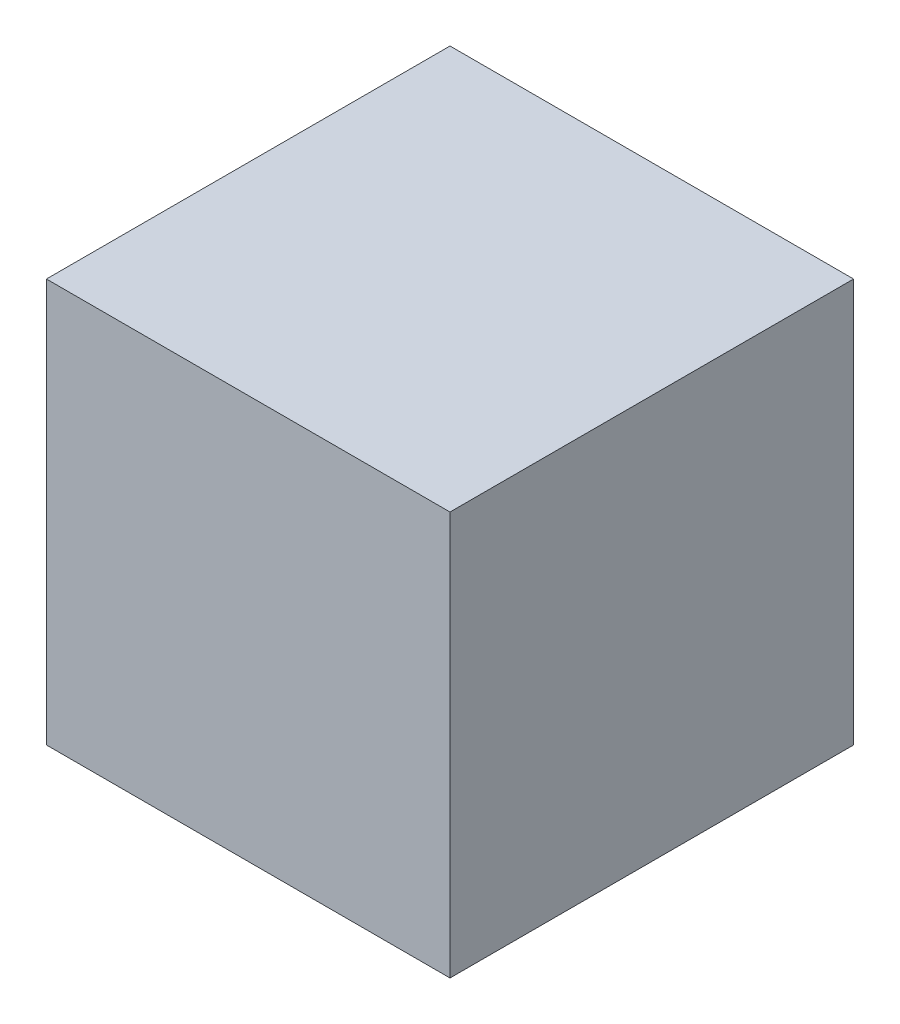
SolidWorks part; units mm, degrees
ref_plane "Front Plane" through (0, 0, 0) normal (0, 0, 1) x (1, 0, 0)
ref_plane "Top Plane" through (0, 0, 0) normal (0, 1, 0) x (1, 0, 0)
ref_plane "Right Plane" through (0, 0, 0) normal (1, 0, 0) x (0, 0, -1)
sketch "Sketch1" plane through (0, 0, 0) normal (0, 0, 1) x (1, 0, 0)
  line L1 (-32.5, -32.5) -> (32.5, -32.5)
  line L2 (-32.5, -32.5) -> (-32.5, 32.5)
  line L3 (-32.5, 32.5) -> (32.5, 32.5)
  line L4 (32.5, -32.5) -> (32.5, 32.5)
  line L5 (-32.5, -32.5) -> (32.5, 32.5) construction
  line L6 (-32.5, 32.5) -> (32.5, -32.5) construction
  point P0 (0, 0)
  dimension "D1" = 65
  dimension "D2" = 65
extrude "Boss-Extrude1" add sketch "Sketch1" along normal blind 32.5 and the other way blind 32.5
sketch "Sketch2" plane through (0, 0, 0) normal (0, 0, 1) x (1, 0, 0)
  line L0 (32.5, 0) -> (-32.5, 0) construction
  line L1 (-32.5, -32.5) -> (32.5, -32.5) construction
  line L2 (-32.5, -32.5) -> (-32.5, 32.5) construction
  line L3 (-32.5, 32.5) -> (32.5, 32.5) construction
  line L4 (32.5, -32.5) -> (32.5, 32.5) construction
  line L5 (-32.5, -32.5) -> (32.5, 32.5) construction
  line L6 (-32.5, 32.5) -> (32.5, -32.5) construction
  line L7 (32.5, 22.981) -> (-32.5, -22.981) construction
  line L8 (32.5, 3.6859) -> (45.9619, 3.6859) construction
  line L9 (32.5, 11.0578) -> (45.9619, 11.0578) construction
  line L10 (32.5, 18.4297) -> (45.9619, 18.4297) construction
  line L11 (32.5, 0) -> (45.9619, 0) construction
  line L12 (45.9619, 18.4297) -> (45.9619, 11.0578) construction
  line L13 (45.9619, 11.0578) -> (45.9619, 3.6859) construction
  line L14 (45.9619, -3.6859) -> (45.9619, 3.6859) construction
  line L15 (32.5, 3.6859) -> (27.1521, 3.6859) construction
  line L16 (32.5, 11.0578) -> (30.7642, 11.0578) construction
  line L17 (32.5, 18.4297) -> (29.8022, 18.4297) construction
  line L18 (29.8022, 18.4297) -> (14.9764, 9.2614) construction
  line L19 (27.1521, 3.6859) -> (24.8573, 3.6859) construction
  line L20 (25.9472, 8.4353) -> (23.671, 8.4353) construction
  line L21 (23.671, 8.4353) -> (21.7275, 7.7427) construction
  line L22 (13.1363, 1.7052) -> (15.9507, 2.0705) construction
  line L23 (15.4785, 4.3734) -> (15.6915, 3.5335) construction
  line L24 (15.7343, 3.3382) -> (15.9375, 2.1696) construction
  line L25 (2.66, 0) -> (0, 0) construction
  line L26 (13.1488, 1.6059) -> (15.9635, 1.9713)
  line L27 (15.9507, 2.0705) -> (22.8739, 2.9691) construction
  line L28 (15.9635, 1.9713) -> (22.9857, 2.8828)
  line L29 (30.7642, 11.0578) -> (28.5958, 11.0578) construction
  line L30 (27.0117, 14.5039) -> (29.1508, 14.5039) construction
  line L31 (16.9152, 4.893) -> (15.451, 4.4695) construction
  line L32 (27.0117, 14.5039) -> (17.2694, 9.2727) construction
  line L33 (19.149, 4.1872) -> (15.7132, 3.4359) construction
  line L34 (23.6102, 8.3074) -> (21.855, 7.682)
  line L35 (27.1521, 3.5859) -> (24.7709, 3.5859)
  line L36 (32.5, 3.5859) -> (27.1521, 3.5859)
  line L37 (32.5, 3.5859) -> (45.9619, 3.5859)
  line L38 (15.9375, 2.1696) -> (22.7616, 3.0554)
  line L39 (23.6537, 8.5353) -> (21.5995, 7.8032)
  line L40 (26.0173, 8.5353) -> (23.6537, 8.5353)
  line L41 (32.5, 3.7859) -> (27.238, 3.7859)
  line L42 (32.5, 3.7859) -> (45.9619, 3.7859)
  line L43 (32.5, 10.9578) -> (45.9619, 10.9578)
  line L44 (32.5, 10.9578) -> (30.7642, 10.9578)
  line L45 (30.7642, 10.9578) -> (28.5272, 10.9578)
  line L46 (26.9708, 14.3684) -> (17.4046, 9.2318)
  line L47 (19.2678, 4.1108) -> (15.7343, 3.3382)
  line L48 (13.1492, 1.606) -> (15.9635, 1.9713) construction
  line L49 (15.9378, 2.1696) -> (22.7616, 3.0554) construction
  line L50 (19.2678, 4.1108) -> (15.7346, 3.3382) construction
  line L51 (19.0296, 4.2635) -> (15.6915, 3.5335)
  line L52 (26.9866, 14.6039) -> (17.1337, 9.3134)
  line L53 (26.9866, 14.6039) -> (29.21, 14.6039)
  line L54 (32.5, 11.1578) -> (30.8323, 11.1578)
  line L55 (32.5, 11.1578) -> (45.9619, 11.1578)
  line L56 (32.5, 18.3297) -> (45.9619, 18.3297)
  line L57 (32.5, 18.3297) -> (29.8307, 18.3297)
  line L58 (29.8307, 18.3297) -> (15.1138, 9.2288)
  line L59 (17.0388, 4.8247) -> (15.4785, 4.3734)
  line L60 (19.0296, 4.2635) -> (15.6919, 3.5336) construction
  line L61 (17.0388, 4.8247) -> (15.4788, 4.3734) construction
  line L62 (16.7911, 4.9612) -> (15.4229, 4.5655)
  line L63 (29.7738, 18.5297) -> (14.8385, 9.2937)
  line L64 (32.5, 18.5297) -> (29.7738, 18.5297)
  line L65 (32.5, 18.5297) -> (45.9619, 18.5297)
  line L66 (16.7911, 4.9612) -> (15.4232, 4.5656) construction
  line L67 (27.8013, 12.687) -> (25.018, 11.4168) construction
  line L68 (26.745, 6.1908) -> (29.868, 6.9935) construction
  line L69 (16.6386, 10.1717) -> (17.1337, 9.3134) construction
  line L70 (20.2806, 10.7761) -> (21.5995, 7.8032) construction
  line L71 (14.8385, 9.2937) -> (13.7083, 10.892) construction
  line L72 (13.1488, 1.6059) -> (13.1488, -1.6059) construction
  line L73 (22.0478, 6.4283) -> (18.9139, 5.5145) construction
  line L74 (18.318, 6.6901) -> (16.634, 6.0751) construction
  line L75 (14.714, 6.4969) -> (16.0168, 7.0721) construction
  arc A0 (27.1521, 3.6859) -> (25.9472, 8.4353) centre (2.66, 0) ccw construction
  arc A1 (24.8573, 3.6859) -> (23.671, 8.4353) centre (0, 0) ccw construction
  arc A2 (21.7275, 7.7427) -> (22.8739, 2.9691) centre (0, 0) cw construction
  arc A3 (30.7642, 11.0578) -> (29.1508, 14.5039) centre (2.66, 0) ccw construction
  arc A4 (28.5958, 11.0578) -> (27.0117, 14.5039) centre (0, 0) ccw construction
  arc A5 (17.2694, 9.2727) -> (19.149, 4.1872) centre (0, 0) cw construction
  arc A6 (14.9764, 9.2614) -> (16.9152, 4.893) centre (0, 0) cw construction
  arc A7 (15.451, 4.4695) -> (13.1329, 9.2864) centre (0, 0) ccw
  arc A8 (15.451, 4.4695) -> (15.7132, 3.4359) centre (0, 0) cw
  arc A9 (15.7132, 3.4359) -> (15.9507, 2.0705) centre (0, 0) cw
  arc A10 (13.1363, 1.7052) -> (13.2465, 0) centre (0, 0) cw
  arc A11 (21.855, 7.682) -> (22.9857, 2.8828) centre (0, 0) cw
  arc A12 (24.7709, 3.5859) -> (23.6102, 8.3074) centre (0, 0) ccw
  arc A13 (21.5995, 7.8032) -> (22.7616, 3.0554) centre (0, 0) cw
  arc A14 (27.238, 3.7859) -> (26.0173, 8.5353) centre (2.66, 0) ccw
  arc A15 (28.5272, 10.9578) -> (26.9708, 14.3684) centre (0, 0) ccw
  arc A16 (17.4046, 9.2318) -> (19.2678, 4.1108) centre (0, 0) cw
  arc A17 (17.1337, 9.3134) -> (19.0296, 4.2635) centre (0, 0) cw
  arc A18 (30.8323, 11.1578) -> (29.21, 14.6039) centre (2.66, 0) ccw
  arc A19 (15.1138, 9.2288) -> (17.0388, 4.8247) centre (0, 0) cw
  arc A20 (14.8385, 9.2937) -> (16.7911, 4.9612) centre (0, 0) cw
  arc A21 (27.238, 3.7859) -> (24.2753, 12.921) centre (0, 0) ccw construction
  arc A22 (28.5272, 10.9578) -> (30.4961, 3.7859) centre (2.66, 0) cw construction
  arc A25 (21.5995, 7.8032) -> (20.2806, 10.7761) centre (0, 0) ccw construction
  arc A26 (17.1337, 9.3134) -> (16.6386, 10.1717) centre (0, 0) ccw construction
  point P0 (0, 0)
  point P9 (0, 0)
  point P12 (0, 0)
  point P21 (45.9619, 0)
  point P114 (14.2734, 10.0928)
  point P116 (13.1488, 0)
  dimension "D1" = 65
  dimension "D2" = 65
  dimension "D3" = 35.264
  dimension "D4" = 13.4619
  dimension "D5" = 0.1
  dimension "D6" = 0.1
  dimension "D7" = 0.1
  dimension "D8" = 0.1
equation "\"size\"= 65mm"
equation "\"offset\"= 0.1mm"
equation "\"D1@Sketch1\"=\"size\""
equation "\"D2@Sketch1\"=\"size\""
equation "\"D1@Boss-Extrude1\"=\"size\"/2"
equation "\"D2@Boss-Extrude1\"=\"size\"/2"
equation "\"D1@Sketch2\"=\"size\""
equation "\"D2@Sketch2\"=\"size\""
equation "\"D3@Sketch2\"=atn(1/sqr(2))"
equation "\"D4@Sketch2\"=\"size\"*(sqr(2)-1)/2"
equation "\"D5@Sketch2\"=\"offset\""
equation "\"D6@Sketch2\"=\"offset\""
equation "\"D7@Sketch2\"=\"offset\""
equation "\"D8@Sketch2\"=\"offset\""
